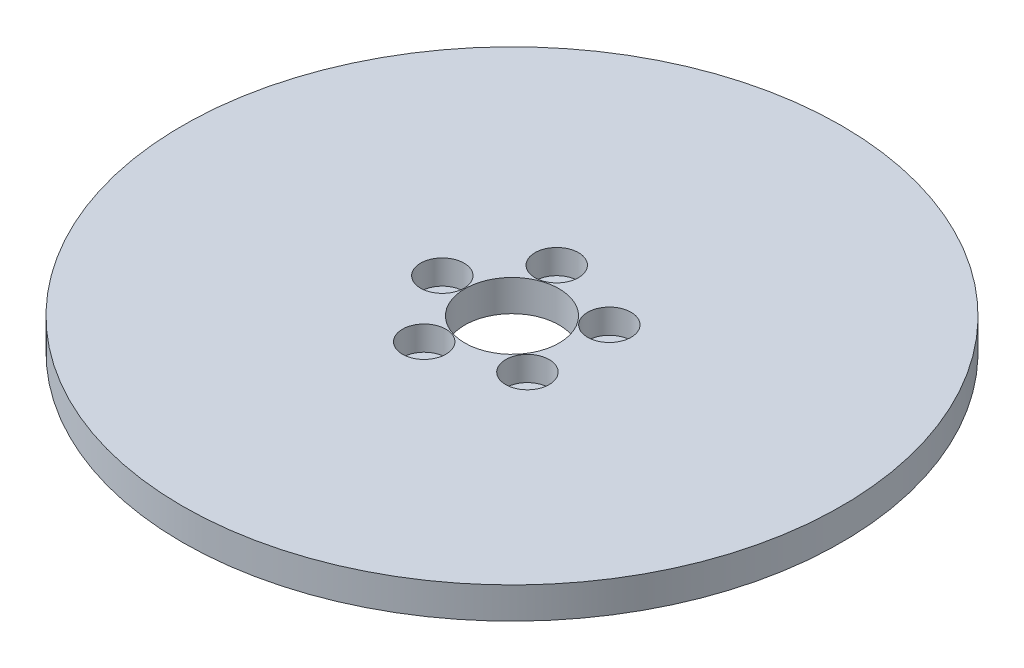
SolidWorks part; units mm, degrees
ref_plane "Front Plane" through (0, 0, 0) normal (0, 0, 1) x (1, 0, 0)
ref_plane "Top Plane" through (0, 0, 0) normal (0, 1, 0) x (1, 0, 0)
ref_plane "Right Plane" through (0, 0, 0) normal (1, 0, 0) x (0, 0, -1)
sketch "Sketch1" plane through (0, 0, 0) normal (0, 1, 0) x (1, 0, 0)
  circle A0 centre (0, 0) radius 52.5
  dimension "FLANGE_OD" = 105
extrude "Boss-Extrude1" add sketch "Sketch1" along normal blind 5
sketch "Sketch2" plane through (0, 0, 0) normal (0, 1, 0) x (1, 0, 0)
  circle A0 centre (0, 0) radius 7.5
  dimension "BORE_D" = 15
extrude "Cut-Extrude1" cut sketch "Sketch2" along normal through all
sketch "Sketch3" plane through (0, 5, 0) normal (0, 1, 0) x (1, 0, 0)
  circle A0 centre (0, 0) radius 11.102 construction
  circle A1 centre (-11.102, 0) radius 3.4623
  dimension "BOLT_D" = 6.9246
  dimension "BOLT_PCD" = 22.2039
extrude "Cut-Extrude2" cut sketch "Sketch3" against normal blind 3.8966
pattern_circular "CirPattern1" count 5 over 360 about axis through (0, 0, 0) along (0, 1, 0) of "Cut-Extrude2"
